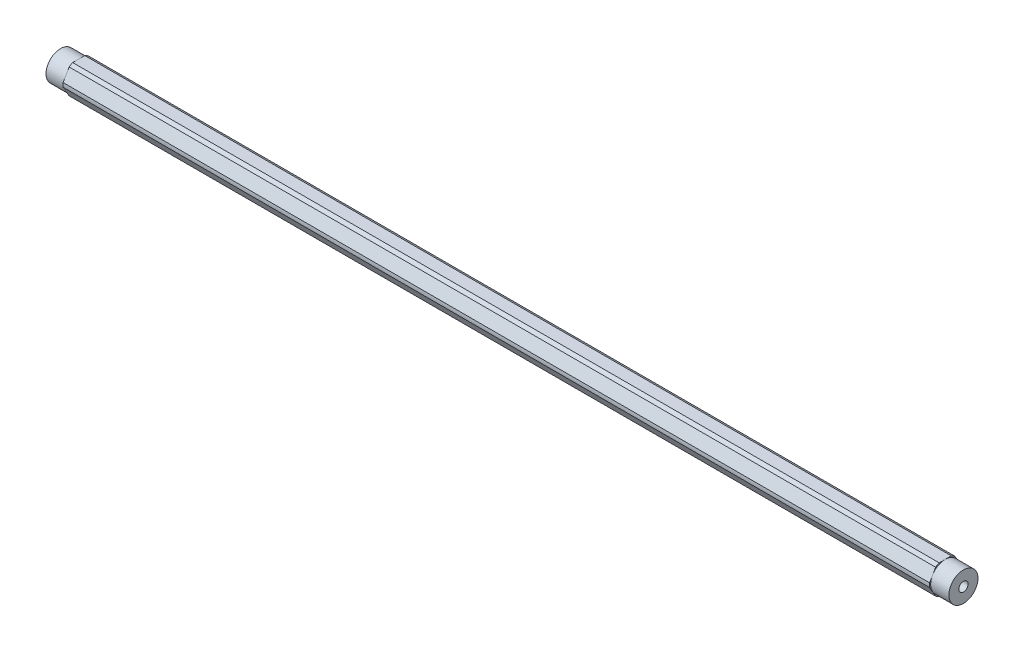
SolidWorks part; units mm, degrees
material "7075-T6 (SN)"
ref_plane "Front Plane" through (0, 0, 0) normal (0, 0, 1) x (1, 0, 0)
ref_plane "Top Plane" through (0, 0, 0) normal (0, 1, 0) x (1, 0, 0)
ref_plane "Right Plane" through (0, 0, 0) normal (1, 0, 0) x (0, 0, -1)
sketch "Sketch1" plane through (0, 0, 0) normal (1, 0, 0) x (0, 0, -1)
  line L1 (3.6662, 6.35) -> (-3.6662, 6.35)
  line L2 (-3.6662, 6.35) -> (-7.3323, 0)
  line L3 (-7.3323, 0) -> (-3.6662, -6.35)
  line L4 (-3.6662, -6.35) -> (3.6662, -6.35)
  line L5 (3.6662, -6.35) -> (7.3323, 0)
  line L6 (7.3323, 0) -> (3.6662, 6.35)
  circle A0 centre (0, 0) radius 2.0193
  circle A1 centre (0, 0) radius 6.875
  circle A2 centre (0, 0) radius 6.35 construction
  dimension "D1" = 13.75
  dimension "D2" = 4.0386
  dimension "D3" = 12.7
extrude "Boss-Extrude1" add sketch "Sketch1" along normal mid plane 393.7 contours L6 A1 L1 L2 L3 L4 L5 A0 region at (0, 5.7918, -3.3439)
sketch "Sketch2" plane through (196.85, 0, 0) normal (1, 0, 0) x (0, 0, -1)
  circle A0 centre (0, 0) radius 6.35
  dimension "D1" = 12.7
extrude "Cut-Extrude-Thin1" cut sketch "Sketch2" against normal blind 7.9375 thin thin type one direction wall 2.54
mirror "Mirror1" about plane through (0, 0, 0) normal (1, 0, 0) of "Cut-Extrude-Thin1"
equation "\"D1@Sketch1\"=13.75mm"
